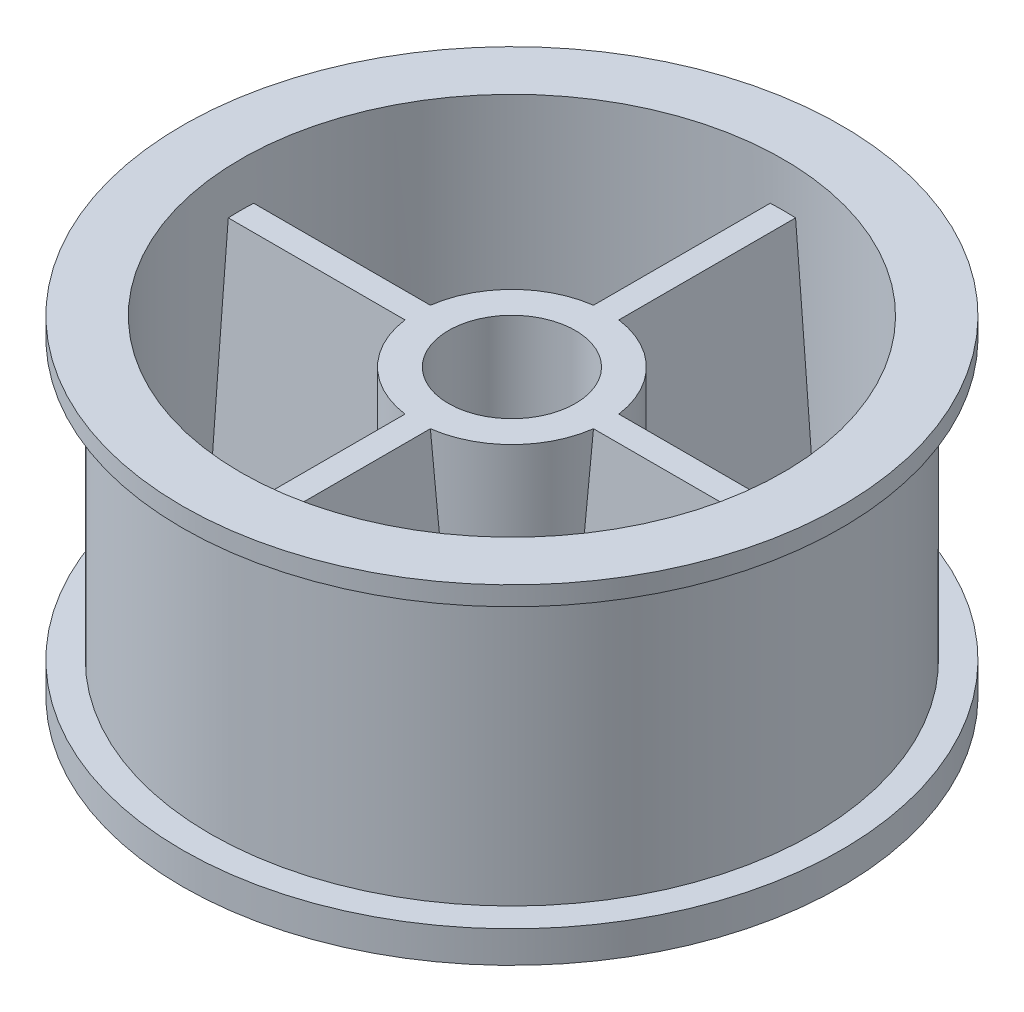
SolidWorks part; units mm, degrees
ref_plane "Front Plane" through (0, 0, 0) normal (0, 0, 1) x (1, 0, 0)
ref_plane "Top Plane" through (0, 0, 0) normal (0, 1, 0) x (1, 0, 0)
ref_plane "Right Plane" through (0, 0, 0) normal (1, 0, 0) x (0, 0, -1)
sketch "Sketch2" plane through (0, 0, 0) normal (1, 0, 0) x (0, 0, -1)
  line L0 (0, 0) -> (26, 0)
  line L1 (26, 0) -> (26, 2.5)
  line L2 (26, 2.5) -> (23.8, 2.5)
  line L3 (23.8, 2.5) -> (23.8, 23.2298)
  line L4 (23.8, 23.2298) -> (26, 24.5)
  line L5 (26, 24.5) -> (26, 26)
  line L6 (26, 26) -> (21.4, 26)
  line L7 (21.4, 26) -> (21.4, 2.5)
  line L8 (21.4, 2.5) -> (0, 2.5)
  line L9 (0, 2.5) -> (0, 0)
  dimension "D1" = 26
  dimension "D2" = 2.5
  dimension "D3" = 1.5
  dimension "D4" = 26
  dimension "D5" = 2.4
  dimension "D6" = 2.2
  dimension "D7" = 2.5
  dimension "D8" = 120
  dimension "D9" = 4.6
revolve "Revolve1" add sketch "Sketch2" angle 360 about L9
sketch "Sketch3" plane through (0, 2.5, 0) normal (0, 1, 0) x (1, 0, 0)
  circle A0 centre (0, 0) radius 7.5
  dimension "D1" = 15
extrude "Boss-Extrude1" add sketch "Sketch3" along normal blind 20
sketch "Sketch4" plane through (0, 22.5, 0) normal (0, 1, 0) x (1, 0, 0)
  circle A0 centre (0, 0) radius 5
  dimension "D1" = 10
extrude "Cut-Extrude1" cut sketch "Sketch4" against normal blind 10
sketch "Sketch5" plane through (0, 12.5, 0) normal (0, 1, 0) x (1, 0, 0)
  circle A0 centre (0, 0) radius 4.25
  dimension "D1" = 8.5
extrude "Cut-Extrude2" cut sketch "Sketch5" against normal through all
sketch "Sketch8" plane through (0, 22.5, 0) normal (0, 1, 0) x (1, 0, 0)
  line L0 (0, 9.7387) -> (0, 19.2143)
  line L1 (0, -11.0021) -> (0, -18.0561)
  line L2 (9.265, 0) -> (19.3722, 0)
  line L3 (-9.1597, 0) -> (-18.4246, 0)
rib "Rib1" sketch "Sketch8" sketch "Sketch8" thickness 2 extrusion direction normal to sketch draft on yes draft angle 5 parameters "D1"=2, "D3"=5
